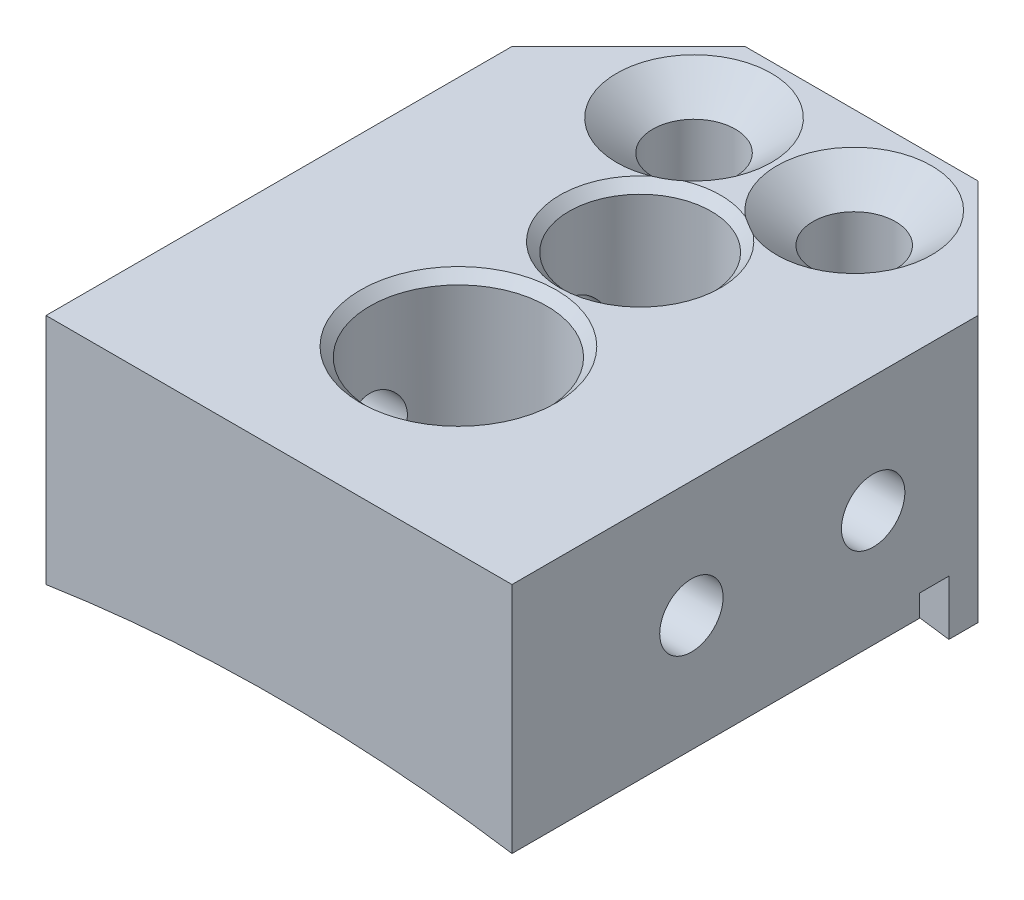
SolidWorks part; units mm, degrees
ref_plane "Front Plane" through (0, 0, 0) normal (0, 0, 1) x (1, 0, 0)
ref_plane "Top Plane" through (0, 0, 0) normal (0, 1, 0) x (1, 0, 0)
ref_plane "Right Plane" through (0, 0, 0) normal (1, 0, 0) x (0, 0, -1)
sketch "Sketch1" plane through (0, 0, 0) normal (0, 1, 0) x (1, 0, 0)
  line L0 (-28.5118, 12.8453) -> (-22.1618, 19.1953)
  line L1 (-22.1618, 19.1953) -> (-9.4618, 19.1953)
  line L2 (-28.5118, 12.8453) -> (-28.5118, -12.5547)
  line L3 (-28.5118, -12.5547) -> (-3.1118, -12.5547)
  line L4 (-3.1118, 12.8453) -> (-3.1118, -12.5547)
  line L5 (-9.4618, 19.1953) -> (-3.1118, 12.8453)
  line L6 (-15.8118, -12.5547) -> (-15.8118, 19.1953) construction
  line L8 (-3.1118, 12.8453) -> (-3.1118, 19.1953) construction
  line L9 (-3.1118, 19.1953) -> (-9.4618, 19.1953) construction
  dimension "D1" = 12.7
  dimension "D2" = 31.75
  dimension "D3" = 25.4
extrude "Boss-Extrude1" add sketch "Sketch1" along normal blind 12.7
sketch "Sketch2" plane through (0, 0, 12.5547) normal (0, 0, 1) x (1, 0, 0)
  circle A0 centre (-15.8118, -82.8523) radius 83.82
  dimension "D1" = 167.64
extrude "Cut-Extrude1" cut sketch "Sketch2" against normal through all both and the other way through all
sketch "Sketch5" plane through (0, 0, -19.1953) normal (0, 0, -1) x (-1, 0, 0)
  line L0 (3.1118, 12.7) -> (3.1118, 0) construction
  line L1 (3.1118, 12.7) -> (3.1118, 0)
  line L4 (28.5118, 12.7) -> (28.5118, 0) construction
  line L5 (28.5118, 12.7) -> (28.5118, 0)
  line L6 (28.5118, -1.7992) -> (28.5118, 0)
  line L7 (3.1118, -1.7992) -> (3.1118, 0)
  line L8 (3.1118, 12.7) -> (28.5118, 12.7)
  arc A0 (3.1118, -1.7992) -> (28.5118, -1.7992) centre (15.8118, -82.8523) cw
  arc A1 (28.5118, 0) -> (3.1118, 0) centre (15.8118, -82.8523) ccw construction
  arc A2 (28.5118, 0) -> (3.1118, 0) centre (15.8118, -82.8523) ccw construction
  dimension "D1" = 82.042
extrude "Boss-Extrude2" add sketch "Sketch5" against normal blind 7.9375
chamfer "Chamfer1" distance 6.35 angle 45 2 edges at (-28.5118, 5.4504, -19.1953) (-3.1118, 5.4504, -19.1953)
hole_wizard "CSK for #8 Flat Head Machine Screw (100)1" positions "Sketch3" profile "Sketch4" countersink size "#8" standard "ANSI Inch" end condition through all
sketch "Sketch3" plane through (0, 12.7, 0) normal (0, 1, 0) x (1, 0, 0)
  line L0 (-15.8118, 19.1953) -> (-15.8118, 3.4006) construction
  line L1 (-9.4618, 19.1953) -> (-22.1618, 19.1953) construction
  point P0 (-20.1775, 14.4328)
  point P12 (-11.4462, 14.4328)
  dimension "D1" = 4.7625
  dimension "D2" = 4.3656
sketch "Sketch4" plane through (-20.1775, 12.7, -14.4328) normal (1, 0, 0) x (0, 0, 1)
  line L0 (0, 0) -> (0, 14.4992)
  line L1 (0, 14.4992) -> (2.2479, 14.4992)
  line L2 (2.2479, 14.4992) -> (2.2479, 1.6518)
  line L3 (2.2479, 1.6518) -> (4.2164, 0)
  line L5 (4.2164, 0) -> (0, 0)
  line L6 (-2.2479, 1.6518) -> (-4.2164, 0) construction
  line L11 (0, -6.35) -> (0, 107.95) construction
  dimension "Thru Hole Dia." = 4.4958
  dimension "Thru Hole Depth" = 14.4992
  dimension "Near C'Sink Dia." = 8.4328
  dimension "Near C'Sink Angle" = 100
sketch "Sketch6" plane through (0, 12.7, 0) normal (0, 1, 0) x (1, 0, 0)
  line L0 (-15.8118, 19.1953) -> (-15.8118, -12.5547) construction
  line L1 (-9.4618, 19.1953) -> (-22.1618, 19.1953) construction
  line L2 (-28.5118, -12.5547) -> (-3.1118, -12.5547) construction
  circle A0 centre (-15.8118, 7.1303) radius 1.6319
  circle A1 centre (-15.8118, -2.7758) radius 1.5239
  spline S0 degree 3 poles (-15.9109, -10.6497) (-15.6088, -10.6497) (-15.4088, -10.6093) (-15.0421, -10.4569) (-14.8723, -10.3433) (-14.6614, -10.1321) (-14.5971, -10.0536) (-14.4867, -9.888) (-14.44, -9.8004) (-14.3254, -9.523) (-14.286, -9.3252) (-14.2863, -9.0237) (-14.2962, -8.9248) (-14.3351, -8.7299) (-14.3646, -8.633) (-14.4412, -8.4488) (-14.488, -8.3613) (-14.5989, -8.1955) (-14.6633, -8.1172) (-14.8743, -7.9067) (-15.0444, -7.7932) (-15.4113, -7.6415) (-15.6118, -7.6017) (-15.9102, -7.6018) (-16.0112, -7.6118) (-16.2064, -7.6508) (-16.3014, -7.6796) (-16.5784, -7.7944) (-16.7462, -7.9063) (-16.9595, -8.1198) (-17.0224, -8.1968) (-17.1327, -8.362) (-17.1804, -8.4512) (-17.2567, -8.6357) (-17.2855, -8.7307) (-17.3244, -8.9262) (-17.3342, -9.0271) (-17.3341, -9.3253) (-17.2941, -9.5259) (-17.142, -9.8926) (-17.0285, -10.0627) (-16.8176, -10.2736) (-16.7392, -10.3379) (-16.5735, -10.4485) (-16.486, -10.4953) (-16.3014, -10.5718) (-16.2047, -10.6011) (-16.0099, -10.6398) (-15.9109, -10.6497) (-15.6088, -10.6497) (-15.4088, -10.6093) knots -0.03125 -0.03125 0 0 0.0625 0.0625 0.125 0.125 0.15625 0.15625 0.1875 0.1875 0.25 0.25 0.28125 0.28125 0.3125 0.3125 0.34375 0.34375 0.375 0.375 0.4375 0.4375 0.5 0.5 0.53125 0.53125 0.5625 0.5625 0.625 0.625 0.65625 0.65625 0.6875 0.6875 0.71875 0.71875 0.75 0.75 0.8125 0.8125 0.875 0.875 0.90625 0.90625 0.9375 0.9375 0.96875 0.96875 1 1 1.0625 1.0625 1.125 only from (-15.8118, -4.2997) to (-15.8118, -4.2997) construction
  spline S2 degree 3 poles (-17.442, 0.8881) (-17.442, 0.5646) (-17.3987, 0.3504) (-17.2355, -0.0422) (-17.1139, -0.2241) (-16.8877, -0.4499) (-16.8036, -0.5187) (-16.6263, -0.6369) (-16.5325, -0.687) (-16.2355, -0.8097) (-16.0236, -0.8519) (-15.7008, -0.8516) (-15.5949, -0.8409) (-15.3862, -0.7993) (-15.2825, -0.7677) (-15.0851, -0.6857) (-14.9915, -0.6355) (-14.814, -0.5168) (-14.7301, -0.4479) (-14.5047, -0.222) (-14.3832, -0.0397) (-14.2207, 0.3532) (-14.178, 0.5678) (-14.1782, 0.8874) (-14.1889, 0.9955) (-14.2306, 1.2046) (-14.2615, 1.3063) (-14.3435, 1.5041) (-14.3946, 1.5994) (-14.5128, 1.7761) (-14.5805, 1.8587) (-14.7329, 2.0109) (-14.8153, 2.0784) (-14.9922, 2.1965) (-15.0878, 2.2476) (-15.2854, 2.3293) (-15.3871, 2.3601) (-15.5964, 2.4017) (-15.7045, 2.4123) (-16.0238, 2.4121) (-16.2385, 2.3692) (-16.6313, 2.2065) (-16.8134, 2.0849) (-17.0392, 1.8591) (-17.1081, 1.7751) (-17.2266, 1.5977) (-17.2767, 1.5039) (-17.3586, 1.3063) (-17.39, 1.2027) (-17.4314, 0.9941) (-17.442, 0.8881) (-17.442, 0.5646) (-17.3987, 0.3504) knots -0.03125 -0.03125 0 0 0.0625 0.0625 0.125 0.125 0.15625 0.15625 0.1875 0.1875 0.25 0.25 0.28125 0.28125 0.3125 0.3125 0.34375 0.34375 0.375 0.375 0.4375 0.4375 0.5 0.5 0.53125 0.53125 0.5625 0.5625 0.59375 0.59375 0.625 0.625 0.65625 0.65625 0.6875 0.6875 0.71875 0.71875 0.75 0.75 0.8125 0.8125 0.875 0.875 0.90625 0.90625 0.9375 0.9375 0.96875 0.96875 1 1 1.0625 1.0625 1.125 only from (-16.218, 5.5497) to (-16.218, 5.5497) construction
  dimension "D1" = 3.2639
  dimension "D2" = 3.0479
  dimension "D3" = 12.065
  dimension "D4" = 21.9711
extrude "Cut-Extrude2" cut sketch "Sketch6" against normal through all
sketch "Sketch7" plane through (-28.5118, 0, 0) normal (-1, 0, 0) x (0, 0, 1)
  line L1 (-11.2578, 0) -> (-9.6703, 0)
  line L2 (-11.2578, 0) -> (-11.2578, 1.1906)
  line L3 (-11.2578, 1.1906) -> (-9.6703, 1.1906)
  line L4 (-9.6703, 0) -> (-9.6703, 1.1906)
  dimension "D1" = 1.5875
  dimension "D2" = 1.1906
extrude "Cut-Extrude3" cut sketch "Sketch7" against normal through all
sketch "Sketch8" plane through (0, 12.7, 0) normal (0, 1, 0) x (1, 0, 0)
  line L0 (-15.8118, 3.2568) -> (-15.8118, 2.0502) construction
  circle A0 centre (-15.8118, -2.7758) radius 4.826
  circle A1 centre (-15.8118, 7.1303) radius 3.8735
  dimension "D2" = 9.652
  dimension "D1" = 7.747
extrude "Cut-Extrude4" cut sketch "Sketch8" against normal through all
chamfer "Chamfer2" distance 0.508 angle 45 2 edges at (-15.8118, 12.7, -3.2568) (-15.8118, 12.7, 7.6018)
hole_wizard "#8-32 Tapped Hole1" positions "Sketch9" profile "Sketch10" tap size "#8-32" standard "ANSI Inch" end condition through all
sketch "Sketch9" plane through (-28.5118, 0, 0) normal (-1, 0, 0) x (0, 0, 1)
  line L0 (7.6018, 12.192) -> (-2.0502, 12.192) construction
  line L1 (-3.2568, 12.192) -> (-11.0038, 12.192) construction
  line L2 (7.6018, 12.192) -> (-2.0502, 12.192)
  line L3 (-3.2568, 12.192) -> (-11.0038, 12.192)
  line L4 (2.7758, 12.7) -> (2.7758, 0) construction
  line L5 (-12.8453, 12.7) -> (12.5547, 12.7) construction
  line L6 (-9.6703, 0) -> (12.5547, 0) construction
  line L8 (-7.1303, 12.7) -> (-7.1303, 0) construction
  point P0 (-7.1303, 6.35)
  point P2 (2.7758, 6.35)
  point P20 (-7.1303, 12.192)
  point P21 (2.7758, 12.192)
  point P22 (0, 0)
  point P23 (0, 0)
sketch "Sketch10" plane through (-28.5118, 6.35, -7.1303) normal (0, 1, 0) x (0, 0, 1)
  line L0 (0, 0) -> (0, 25.4)
  line L1 (0, 25.4) -> (1.7272, 25.4)
  line L2 (1.7272, 25.4) -> (1.7272, 0)
  line L5 (1.7272, 0) -> (0, 0)
  line L11 (0, -6.35) -> (0, 107.95) construction
  dimension "Thru Tap Drill Dia." = 3.4544
  dimension "Thru Tap Drill Depth" = 25.4
cosmetic thread "Hole Thread1" parameters "D2"=4.1656
cosmetic thread "Hole Thread2" parameters "D2"=4.1656
